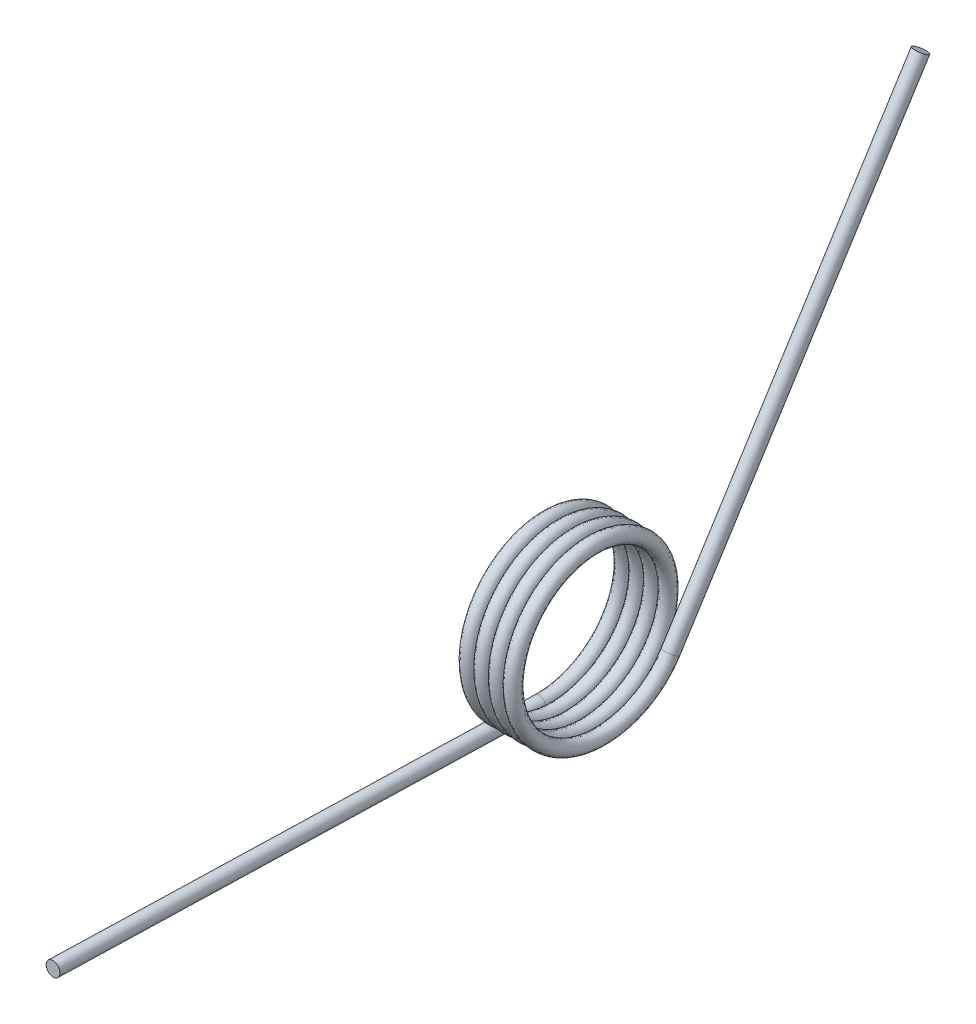
SolidWorks part; units mm, degrees
ref_plane "Front" through (0, 0, 0) normal (0, 0, 1) x (1, 0, 0)
ref_plane "Top" through (0, 0, 0) normal (0, 1, 0) x (1, 0, 0)
ref_plane "Right" through (0, 0, 0) normal (1, 0, 0) x (0, 0, -1)
sketch "Sketch1" plane through (0, 0, 0) normal (1, 0, 0) x (0, 0, -1)
  line L0 (0, -3.9751) -> (0, -4.7371) construction
  line L1 (4.1024, -2.3686) -> (16.8024, 19.6285) construction
  line L2 (0, -4.7371) -> (-25.4, -4.7371) construction
  line L3 (0, 0) -> (4.7371, 0) construction
  line L4 (0, 0) -> (4.1024, -2.3686) construction
  line L5 (-25.4, -4.7371) -> (-25.4, -3.9751) construction
  line L6 (-25.4, -3.9751) -> (0, -3.9751) construction
  line L7 (16.8024, 19.6285) -> (16.1425, 20.0095) construction
  line L8 (16.1425, 20.0095) -> (3.4425, -1.9876) construction
  circle A0 centre (0, 0) radius 4.7371 construction
  circle A1 centre (0, 0) radius 3.175 construction
  circle A2 centre (0, 0) radius 4.3561 construction
  point P7 (0, -4.3561)
  point P10 (0, 4.7371)
  dimension "OD" = 9.4742
  dimension "For Shaft Diameter" = 6.35
  dimension "Wire Diameter" = 0.762
  dimension "Leg Length" = 25.4
  dimension "Deflection Angle" = 120
sketch "Sketch2" plane through (0, 0, 0) normal (1, 0, 0) x (0, 0, -1)
  circle A0 centre (0, 0) radius 4.3561 construction
  circle A2 centre (0, 0) radius 4.3561
curve "Helix/Spiral1" pitch 0.7874 height 3.2808 turns 4.1667
ref_plane "Plane1" through (0, -4.3561, 0) normal (0.0288, 0, -0.9996) x (0.9993, -0.0232, 0.0287)
sketch "Sketch3" plane through (0, -4.3561, 0) normal (0.0288, 0, -0.9996) x (0.9993, -0.0232, 0.0287)
  circle A0 centre (0, 0) radius 0.381
  dimension "D1" = 0.762
sweep "Sweep1" add profiles "Sketch3" path "Helix/Spiral1"
sketch "Sketch4" plane through (0, 0, 0) normal (-0.0288, 0, 0.9996) x (-0.9993, 0.0232, -0.0287)
  circle A1 centre (-0.1012, 4.3549) radius 0.381
  circle A2 centre (-0.1012, 4.3549) radius 0.381
  dimension "D1" = 0
extrude "Extrude1" add sketch "Sketch4" along normal blind 25.4
sketch "Sketch5" plane through (0.0027, 0.0817, -0.0472) normal (0.0288, 0.8657, -0.4998) x (0.9987, -0.0463, -0.0228)
  circle A1 centre (3.4635, 4.2113) radius 0.381
  circle A2 centre (3.4635, 4.2113) radius 0.381
  dimension "D1" = 0
extrude "Extrude2" add sketch "Sketch5" along normal blind 25.4
sketch "Sketch6" plane through (0, 0, 0) normal (1, 0, 0) x (0, 0, -1)
  circle A2 centre (0, 0) radius 3.9751 construction
equation "\"D4@Helix/Spiral1\" = \"Wire Diameter@Sketch1\" + .001"
equation "\"D1@Sketch3\"=\"Wire Diameter@Sketch1\""
equation "\"D1@Extrude2\"=\"Leg Length@Sketch1\""
equation "\"Leg Length@Extrude1\"=\"Leg Length@Sketch1\""
